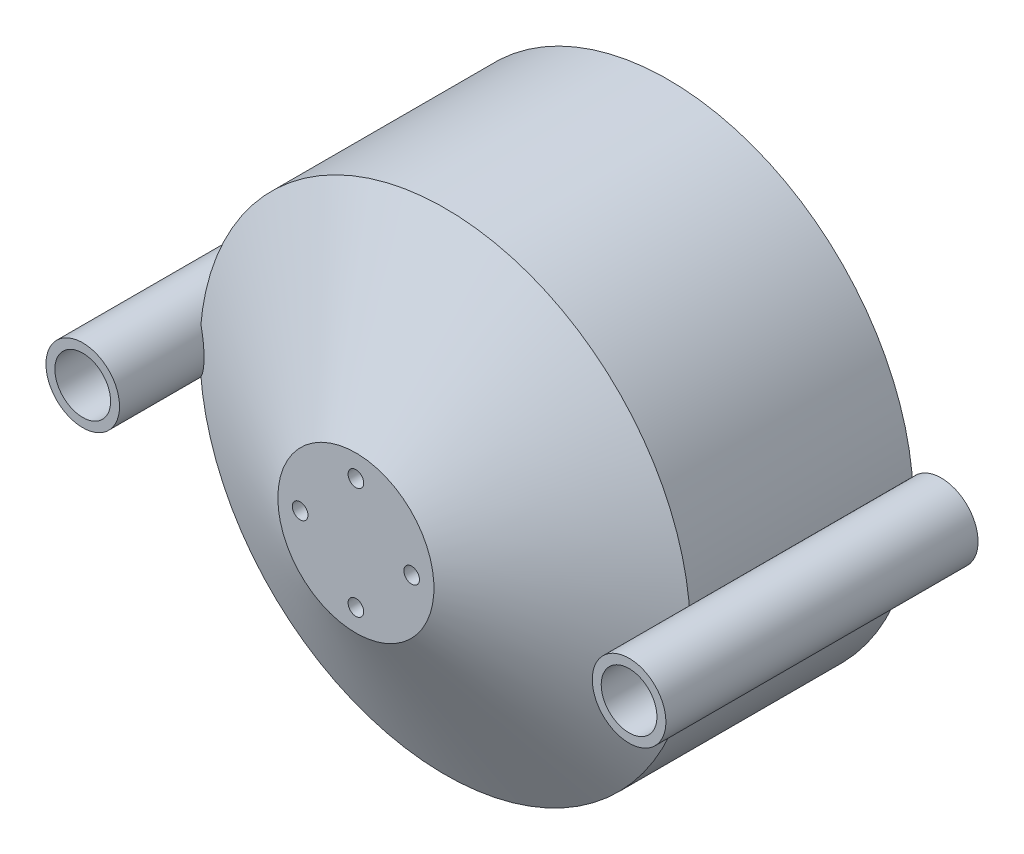
SolidWorks part; units mm, degrees
ref_plane "Front Plane" through (0, 0, 0) normal (0, 0, 1) x (1, 0, 0)
ref_plane "Top Plane" through (0, 0, 0) normal (0, 1, 0) x (1, 0, 0)
ref_plane "Right Plane" through (0, 0, 0) normal (1, 0, 0) x (0, 0, -1)
sketch "Sketch2" plane through (0, 0, 0) normal (0, 1, 0) x (1, 0, 0)
  line L0 (0, 52.2554) -> (0, -57.8804) construction
  line L1 (0, 0) -> (-17.5, 0)
  line L2 (-17.5, 0) -> (-55, 20)
  line L3 (-55, 20) -> (-55, 70)
  line L4 (-23.4375, 6) -> (-52.5, 21.5)
  line L5 (-52.5, 21.5) -> (-52.5, 70)
  line L6 (-55, 70) -> (-52.5, 70)
  line L7 (0, 6) -> (-15, 6)
  line L9 (-16.3235, 2.2059) -> (-52.5, 21.5) construction
  line L10 (0, 6) -> (0, 0)
  line L11 (-15, 6) -> (-23.4375, 6)
  dimension "D1" = 17.5
  dimension "D2" = 55
  dimension "D3" = 20
  dimension "D4" = 50
  dimension "D6" = 6
  dimension "D5" = 2.5
revolve "Revolve1" add sketch "Sketch2" angle 360 about L0
sketch "Sketch3" plane through (0, 0, 0) normal (0, 0, 1) x (1, 0, 0)
  line L0 (0, 17.5) -> (0, -17.5) construction
  circle A0 centre (0, 0) radius 17.5 construction
  circle A1 centre (0, 12.5) radius 1.75
  circle A2 centre (12.5, 0) radius 1.75
  circle A3 centre (0, -12.5) radius 1.75
  circle A4 centre (-12.5, 0) radius 1.75
  point P17 (0, 0)
  dimension "D1" = 3.5
  dimension "D2" = 12.5
  dimension "D3" = 4
extrude "Cut-Extrude1" cut sketch "Sketch3" against normal through all
sketch "Sketch4" plane through (0, 0, 0) normal (0, 0, 1) x (1, 0, 0)
  line L0 (-78.8993, 0) -> (75.1229, 0) construction
  line L1 (0, 76.3912) -> (0, -75.6965) construction
  circle A1 centre (0, 0) radius 55 construction
  circle A2 centre (-61.25, 0) radius 8.25
  circle A3 centre (-61.25, 0) radius 6.25
  circle A4 centre (61.25, 0) radius 8.25
  circle A5 centre (61.25, 0) radius 6.25
  dimension "D1" = 12.5
  dimension "D2" = 2
  dimension "D3" = 110
extrude "Boss-Extrude1" add sketch "Sketch4" against normal up to surface (70 mm away) separate body up to face at (-55, 0, -70)
